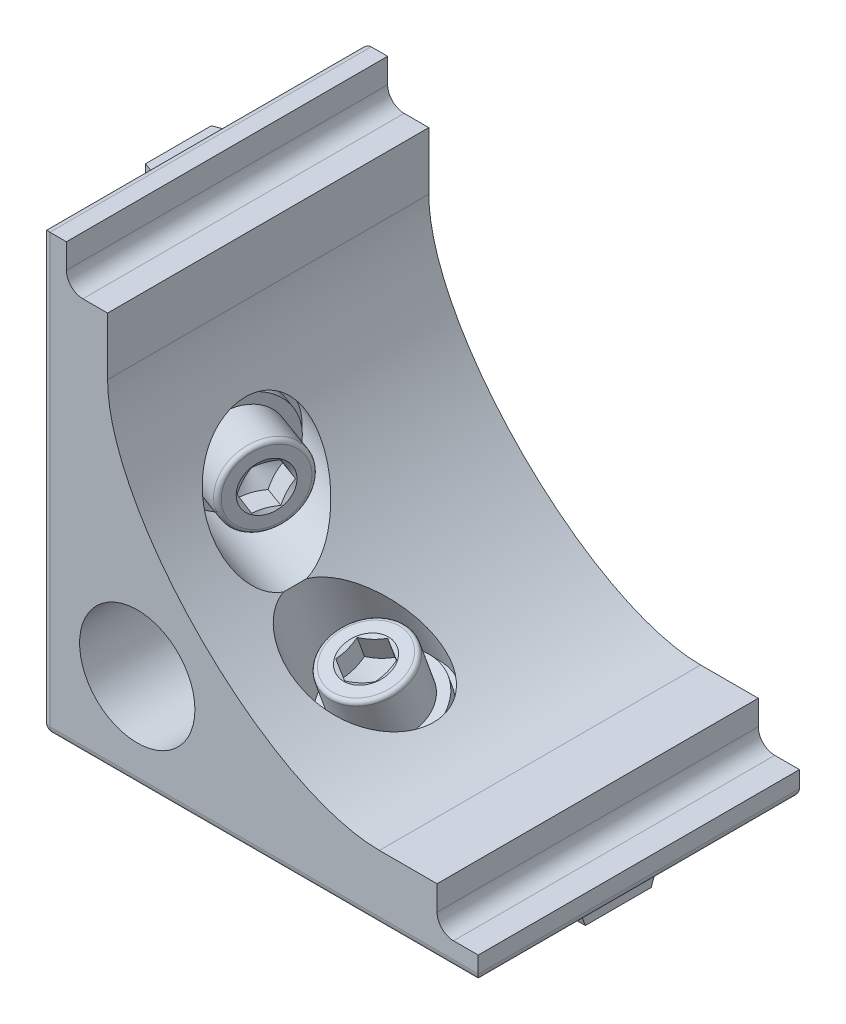
SolidWorks part; units mm, degrees
ref_plane "Front Plane" through (0, 0, 0) normal (0, 0, 1) x (1, 0, 0)
ref_plane "Top Plane" through (0, 0, 0) normal (0, 1, 0) x (1, 0, 0)
ref_plane "Right Plane" through (0, 0, 0) normal (1, 0, 0) x (0, 0, -1)
sketch "Sketch1" plane through (0, 0, 0) normal (0, 0, 1) x (1, 0, 0)
  line L0 (27, 0) -> (-26, 0) construction
  line L1 (-26, 0) -> (-26, 53) construction
  line L2 (-12.5, -2.9) -> (12.5, -2.9) construction
  line L3 (0, 0) -> (0, 7.25) construction
  circle A0 centre (0, 7.25) radius 3 construction
  point P3 (0, 0)
  point P8 (0, -2.9)
  dimension "D3" = 6
  dimension "Height" = 53
  dimension "Offset" = 26
  dimension "D1" = 2.9
  dimension "Length" = 25
  dimension "D2" = 53
  dimension "D4" = 7.25
sketch "Sketch2" plane through (0, 0, 0) normal (1, 0, 0) x (0, 0, -1)
  line L0 (-19.5, 0) -> (19.5, 0) construction
  line L1 (-3, -2.9) -> (3, -2.9) construction
  line L3 (0, 0) -> (0, 53) construction
  line L4 (3, -2.9) -> (3, -3.9) construction
  point P4 (0, 0)
  point P8 (0, -2.9)
  dimension "Width" = 39
  dimension "Thread Size" = 6
  dimension "Thread Pitch" = 1
sketch "Sketch3" plane through (0, 0, 0) normal (0, 0, 1) x (1, 0, 0)
  line L4 (-26, 53) -> (-23, 53)
  line L5 (-23, 53) -> (-23, 48)
  line L6 (-23, 48) -> (-18, 48)
  line L7 (-18, 48) -> (-18, 41)
  line L10 (27, 0) -> (-26, 0) construction
  line L11 (-26, 0) -> (27, 0)
  line L12 (27, 0) -> (27, 3)
  line L13 (27, 3) -> (22, 3)
  line L14 (22, 3) -> (22, 8)
  line L15 (22, 8) -> (15, 8)
  line L16 (-18, 41) -> (-18, 27.3418) construction
  line L17 (-18, 27.3418) -> (1.3418, 8) construction
  line L18 (1.3418, 8) -> (15, 8) construction
  line L19 (-26, 0) -> (-14.4, 11.6) construction
  line L20 (-14.4, 11.6) -> (-8.3291, 17.6709) construction
  line L21 (-9.4503, 16.5497) -> (-6.6218, 19.3782) construction
  line L22 (-26, 53) -> (-26, 0)
  circle A0 centre (-14.4, 11.6) radius 7
  spline S0 degree 3 poles (-18, 41) (-18, 27.3418) (1.3418, 8) (15, 8) knots 0 0 0 0 1 1 1 1
  dimension "D11" = 14
  dimension "D1" = 12
  dimension "D2" = 5
  dimension "D3" = 8
  dimension "D4" = 45
  dimension "D5" = 11.6
  dimension "D6" = 12
  dimension "D7" = 5
  dimension "D12" = 4
extrude "Boss-Extrude1" add sketch "Sketch3" along normal mid plane 39
sketch "Sketch6" plane through (0, 0, 0) normal (1, 0, 0) x (0, 0, -1)
  line L0 (-4, -2.9) -> (4, -2.9)
  line L2 (4, -2.9) -> (5.0555, 0)
  line L3 (-19.5, 0) -> (19.5, 0) construction
  line L4 (5.0555, 0) -> (-5.0555, 0)
  line L5 (-5.0555, 0) -> (-4, -2.9)
  line L6 (0, 0) -> (0, 53) construction
  point P3 (0, -2.9)
  dimension "D1" = 8
  dimension "D2" = 20
extrude "Boss-Extrude2" add sketch "Sketch6" along normal mid plane 49
fillet "Fillet1" radius 2 2 edges at (-23, 48, 0) (22, 3, 0)
fillet "Fillet2" radius 1 7 edges at (0.5, 0, -19.5) (27, 0, 0) (0.5, 0, 19.5) (-26, 26.5, -19.5) (-26, 53, 0) (-26, 26.5, 19.5) (-26, 0, 0)
sketch "Sketch7" plane through (0, 0, 0) normal (1, 0, 0) x (0, 0, -1)
  line B0 (5.9518, -10.4811) -> (7.2578, -9.1838)
  line B1 (7.8162, -4.7642) -> (5.5241, -5.5446)
  line B2 (5.5241, -5.5446) -> (4, -2.9)
  line B3 (4, -2.9) -> (-4, -2.9)
  line B4 (-4, -2.9) -> (-5.5262, -5.5434)
  line B5 (-5.5262, -5.5434) -> (-7.8014, -4.7153)
  line B6 (-7.2827, -9.135) -> (-5.9855, -10.4409)
  line B7 (0.3137, -12.5332) -> (5.9518, -10.4811)
  line B8 (0, -2.9) -> (0, -5.4471) construction
  arc B9 (7.2578, -9.1838) -> (8.808, -5.4767) centre (3.558, -5.4591) ccw
  arc B10 (8.808, -5.4767) -> (7.8162, -4.7642) centre (8.058, -5.4742) ccw
  arc B11 (-7.8014, -4.7153) -> (-8.808, -5.4175) centre (-8.058, -5.42) ccw
  arc B12 (-8.808, -5.4175) -> (-7.2827, -9.135) centre (-3.558, -5.4351) ccw
  arc B13 (-5.9855, -10.4409) -> (0.3137, -12.5332) centre (-0.7667, -5.2571) ccw
sketch_block_instance "Block-Sketch6-1"
sketch_block "Block-Sketch6" parameters "D1"=0.75, "D10"=5.25, "D2"=70, "D3"=0.193, "D4"=30, "D5"=20, "D6"=6, "D7"=8, "D8"=17.6159, "D9"=9.1595, "D11"=45, "D12"=45
extrude "Boss-Extrude3" add sketch "Sketch7" along normal mid plane 25 separate body
sketch "Sketch8" plane through (0, 0, 0) normal (1, 0, 0) x (0, 0, -1)
  line L0 (3.1327, -11.5071) -> (-12.8774, 32.4803)
  line L1 (0.3137, -12.5332) -> (5.9518, -10.4811) construction
  line L2 (-12.8774, 32.4803) -> (-19.2203, 30.1717)
  line L3 (-19.2203, 30.1717) -> (-9.9858, 4.8)
  line L4 (-9.9858, 4.8) -> (-6.4619, 6.0826)
  line L5 (-6.4619, 6.0826) -> (0.3137, -12.5332)
  line L6 (0.3137, -12.5332) -> (3.1327, -11.5071)
  line L7 (-6.9703, 16.2507) -> (3.1327, -11.5071) construction
  line L8 (-19.5, 0) -> (19.5, 0) construction
  dimension "D1" = 6
  dimension "D2" = 4.8
  dimension "D3" = 13.5
  dimension "D4" = 27
revolve "Cut-Revolve1" cut sketch "Sketch8" angle 360 about L7
sketch "Sketch9" plane through (0, 0, 0) normal (1, 0, 0) x (0, 0, -1)
  line L0 (3.1327, -11.5071) -> (-4.667, 9.9224)
  line L1 (3.1327, -11.5071) -> (-12.8774, 32.4803) construction
  line L2 (-4.667, 9.9224) -> (-7.3962, 10.4036)
  line L3 (-7.3962, 10.4036) -> (-8.3812, 13.11)
  line L4 (-8.3812, 13.11) -> (-10.6364, 12.2891)
  line L5 (-10.6364, 12.2891) -> (-8.6664, 6.8765)
  line L6 (-8.6664, 6.8765) -> (-6.975, 7.4921)
  line L7 (-6.975, 7.4921) -> (0.04, -11.7814)
  line L8 (0.04, -11.7814) -> (1.0654, -12.2596)
  line L9 (0.3137, -12.5332) -> (3.1327, -11.5071) construction
  line L10 (1.0654, -12.2596) -> (3.1327, -11.5071)
  line L11 (-4.667, 9.9224) -> (-12.8774, 32.4803) construction
  line L12 (-6.4619, 6.0826) -> (-9.3515, 5.0309)
  line L13 (-9.9858, 4.8) -> (-6.4619, 6.0826) construction
  line L14 (-9.3515, 5.0309) -> (-9.8645, 6.4404)
  line L15 (-9.8645, 6.4404) -> (-8.6664, 6.8765)
  line L16 (-68410.9989, 187954.7748) -> (68407.1614, -187950.0313) construction
  dimension "D1" = 6
  dimension "D2" = 4.8
  dimension "D3" = 12.15
  dimension "D4" = 1.5
  dimension "D5" = 9.6
  dimension "D6" = 5.76
  dimension "D7" = 60
  dimension "D8" = 2.88
  dimension "D9" = 45
  dimension "D10" = 0.8
revolve "Revolve1" add sketch "Sketch9" angle 360 about L11 region at (0, 0.7451, 3.2798)
revolve "Revolve2" add sketch "Sketch9<3>" angle 360 about L11 region at (0, 6.2615, 8.1632)
sketch "Sketch9<3>" plane through (0, 0, 0) normal (1, 0, 0) x (0, 0, -1) same geometry as "Sketch9"
sketch "Sketch10" plane through (0, 14.27, 5.1939) normal (0, 0.9397, 0.342) x (1, 0, 0)
  line L1 (0, 1.7794) -> (-2.4, 0.3938)
  line L2 (-2.4, 0.3938) -> (-2.4, -2.3775)
  line L3 (-2.4, -2.3775) -> (0, -3.7631)
  line L4 (0, -3.7631) -> (2.4, -2.3775)
  line L5 (2.4, -2.3775) -> (2.4, 0.3938)
  line L6 (2.4, 0.3938) -> (0, 1.7794)
  circle A0 centre (0, -0.9919) radius 2.4 construction
  circle A1 centre (0, -0.9919) radius 2.4 construction
extrude "Cut-Extrude3" cut sketch "Sketch10" against normal up to surface (2.6656 mm away) up to face at (0, 12.0453, 2.8856)
sketch "Sketch11" plane through (0, 14.27, 5.1939) normal (0, 0.9397, 0.342) x (1, 0, 0)
  circle A0 centre (0, -0.9919) radius 2.88
  dimension "D1" = 5.76
extrude "Cut-Extrude4" cut sketch "Sketch11" against normal through all draft 60
fillet "Fillet3" radius 0.5 1 edges at (0, 15.5725, 1.6154)
ref_plane "Plane1" through (-13, 13, 0) normal (0.7071, -0.7071, 0) x (0.7071, 0.7071, 0)
mirror "Mirror1" about plane through (-13, 13, 0) normal (0.7071, -0.7071, 0) of "Boss-Extrude2", "Cut-Revolve1"
mirror "Mirror2" about plane through (-13, 13, 0) normal (0.7071, -0.7071, 0) of bodies 118 117 116
equation "\"D1@Boss-Extrude1\"=\"Width@Sketch2\""
equation "\"D1@Boss-Extrude3\"=\"Length@Sketch1\""
equation "\"D1@Sketch8\"=\"Thread Size@Sketch2\""
equation "\"D2@Sketch8\"=\"D1@Sketch8\"*.8"
equation "\"D3@Sketch8\"=\"D1@Sketch8\"*2.25"
equation "\"D4@Sketch8\"=\"D3@Sketch8\"*2"
equation "\"D1@Sketch9\"=\"Thread Size@Sketch2\""
equation "\"D2@Sketch9\"=\"D1@Sketch9\"*.8"
equation "\"D3@Sketch9\"=\"D3@Sketch8\"*.9"
equation "\"D4@Sketch9\"=\"D1@Sketch9\"*.25"
equation "\"D5@Sketch9\"=\"D2@Sketch9\"*2"
equation "\"D6@Sketch9\"=\"D5@Sketch9\"*.6"
equation "\"D8@Sketch9\"=\"D6@Sketch9\"*.5"
equation "\"D10@Sketch9\"=\"Thread Pitch@Sketch2\"*.8"
equation "\"D1@Sketch11\"=\"D2@Sketch9\"*1.2"
